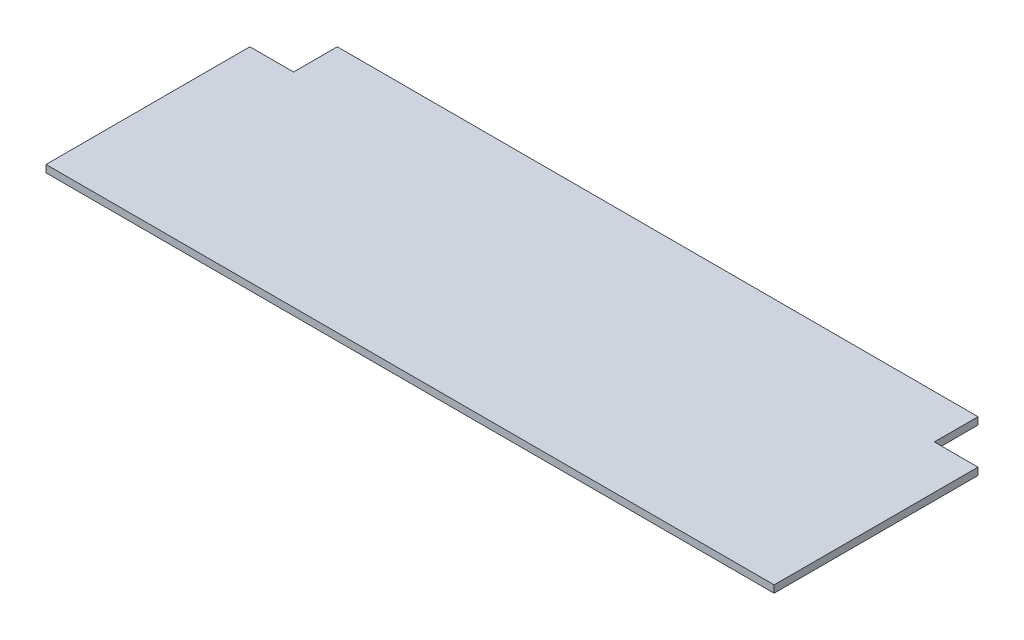
SolidWorks part; units mm, degrees
material "Custom Plastic"
ref_plane "Front Plane" through (0, 0, 0) normal (0, 0, 1) x (1, 0, 0)
ref_plane "Top Plane" through (0, 0, 0) normal (0, 1, 0) x (1, 0, 0)
ref_plane "Right Plane" through (0, 0, 0) normal (1, 0, 0) x (0, 0, -1)
sketch "Sketch1" plane through (0, 0, 0) normal (0, 1, 0) x (1, 0, 0)
  line L1 (0, 0) -> (635, 0)
  line L2 (0, 0) -> (0, 215.9)
  line L3 (0, 215.9) -> (635, 215.9)
  line L4 (635, 0) -> (635, 215.9)
  dimension "D1" = 215.9
  dimension "D2" = 635
extrude "Boss-Extrude1" add sketch "Sketch1" along normal blind 6.35
sketch "Sketch2" plane through (0, 6.35, 0) normal (0, 1, 0) x (1, 0, 0)
  line L1 (0, 215.9) -> (38.1, 215.9)
  line L2 (0, 215.9) -> (0, 177.8)
  line L3 (0, 177.8) -> (38.1, 177.8)
  line L4 (38.1, 215.9) -> (38.1, 177.8)
  line L5 (635, 215.9) -> (596.9, 215.9)
  line L6 (635, 215.9) -> (635, 177.8)
  line L7 (635, 177.8) -> (596.9, 177.8)
  line L8 (596.9, 215.9) -> (596.9, 177.8)
  dimension "D1" = 38.1
  dimension "D2" = 38.1
  dimension "D3" = 38.1
  dimension "D4" = 38.1
extrude "Cut-Extrude1" cut sketch "Sketch2" against normal through all
